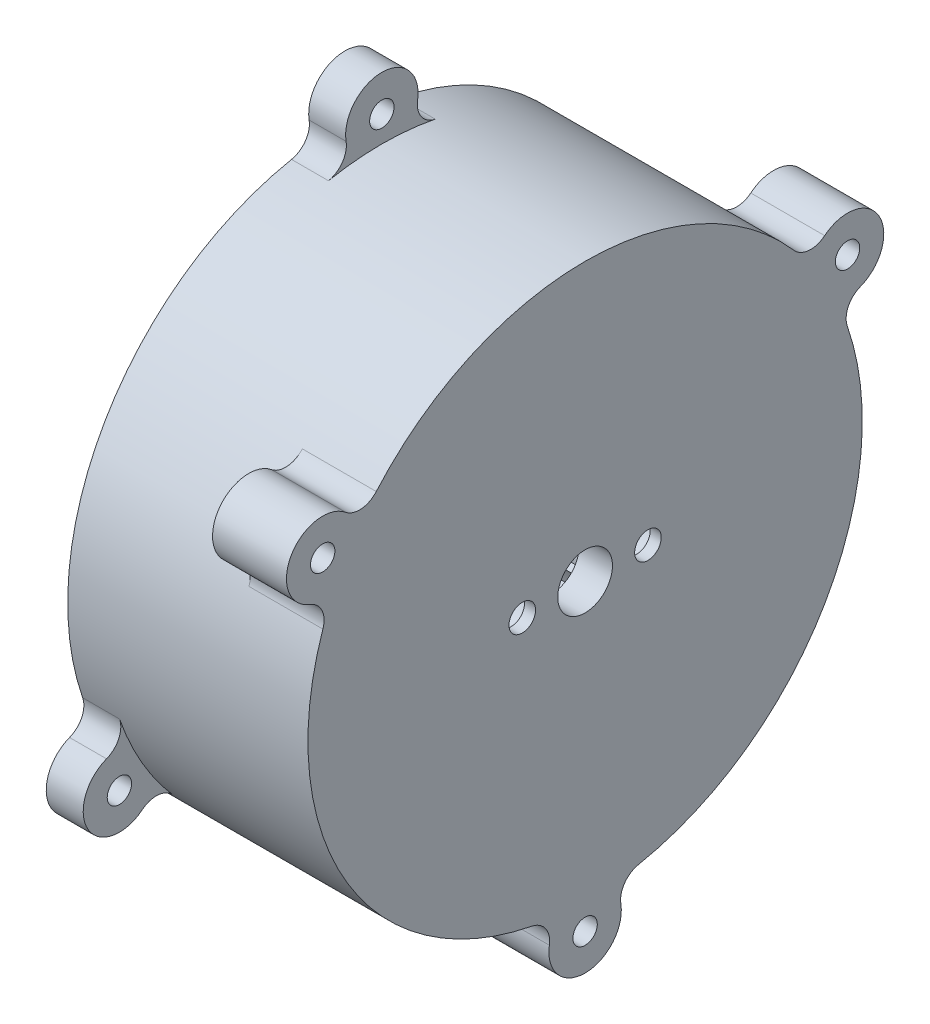
SolidWorks part; units mm, degrees
ref_plane "Plane1" through (0, 0, 0) normal (0, 0, 1) x (1, 0, 0)
ref_plane "Plane2" through (0, 0, 0) normal (0, 1, 0) x (1, 0, 0)
ref_plane "Plane3" through (0, 0, 0) normal (1, 0, 0) x (0, 0, -1)
sketch "HoldingSke" plane through (0, 0, 0) normal (0, 1, 0) x (1, 0, 0)
  line L0 (0, 0) -> (0.4589, -0.6553)
  line L1 (-15, 0) -> (100, 0) construction
  line L2 (0, 0) -> (-2.1039, 2.3779)
  line L3 (0, 0) -> (-11.863, 4.5341)
  line L4 (0, 0) -> (4.9534, 7.0742)
  line L5 (0, 0) -> (-23.7986, -8.8762)
  line L6 (0, 0) -> (-10.5278, -7.1032)
  line L7 (-2.1039, 2.3779) -> (3.3635, 27.1825)
  line L8 (-76.2, 3.6279) -> (-54.61, 3.6279)
  line L9 (-67.7845, 28.3722) -> (-49.3413, 33.142)
  line L10 (-76.2, 71.12) -> (104.1128, 71.12)
  line L11 (0, 0) -> (-28, 0)
  line L12 (-76.2, 101.6) -> (-76.155, 101.6)
  line L13 (24.9733, 27.94) -> (52.9518, 28.4284)
  line L14 (24.9733, 27.94) -> (24.9743, 27.94)
  line L15 (24.9733, 27.94) -> (100.4006, 29.5858)
  circle A0 centre (0, 0) radius 37.5
  circle A1 centre (0, 0) radius 12.7
  circle A2 centre (0, 0) radius 12.7
  dimension "Num_teeth" = 55
  dimension "Pitch_radius" = 180.3128
  dimension "Width" = 28
  dimension "Diameter" = 75
sketch "BasProSke" plane through (0, 0, 0) normal (0, 1, 0) x (1, 0, 0)
  line L0 (-10, 0) -> (60, 0) construction
  line L1 (0, 33.125) -> (0, 37.5)
  line L2 (0, 33.125) -> (28, 33.125)
  line L3 (28, 33.125) -> (28, 37.5)
  line L4 (28, 37.5) -> (0, 37.5)
  dimension "Thickness" = 28
  dimension "Diameter" = 75
revolve "Base-Revolve" add sketch "BasProSke" angle 360 about L0
sketch "TooCutSke" plane through (0, 0, 0) normal (1, 0, 0) x (0, 0, -1)
  line L3 (1.0941, 34.3576) -> (1.0941, 53.6633) construction
  line L4 (0, 0) -> (0, 59.563) construction
  line L5 (0, 0) -> (-3.9007, 68.2161) construction
  line L6 (-15.2783, 29.1274) -> (36.0712, 32.0636) construction
  circle A0 centre (0, 0) radius 34.375 construction
  circle A1 centre (0, 0) radius 35.9385 construction
  circle A2 centre (0, 0) radius 29.9521 construction
  circle A3 centre (0, 0) radius 33.0996 construction
  arc A4 (1.4514, 33.0678) -> (0.5036, 35.935) centre (-15.2783, 29.1274) ccw
  arc A5 (1.4514, 33.0678) -> (-1.4514, 33.0678) centre (0, 0) ccw
  arc A6 (0.5036, 35.935) -> (-0.5036, 35.935) centre (0, 0) ccw
  arc A7 (-0.5036, 35.935) -> (-1.4514, 33.0678) centre (15.2783, 29.1274) ccw
extrude "ToothCut" cut sketch "TooCutSke" along normal through all
fillet "Breaks" [suppressed] radius 0.125
fillet "RootFillets" [suppressed] radius 0.3135
pattern_circular "TeethCuts" count 55 every 6.545 about axis through (-10, 0, 0) along (1, 0, 0) of "RootFillets", "Breaks", "ToothCut"
sketch "Sketch1" plane through (28, 0, 0) normal (1, 0, 0) x (0, 0, -1)
  circle A0 centre (0, 0) radius 37.5
extrude "Boss-Extrude1" add sketch "Sketch1" along normal blind 4.5
sketch "Sketch2" plane through (32.5, 0, 0) normal (1, 0, 0) x (0, 0, -1)
  circle A0 centre (0, 0) radius 3.7
  circle A1 centre (-8.5, 0) radius 1.8
  circle A2 centre (8.5, 0) radius 1.8
  dimension "D1" = 7.4
  dimension "D2" = 3.6
  dimension "D3" = 8.5
  dimension "D4" = 8.5
extrude "Cut-Extrude1" cut sketch "Sketch2" against normal blind 4.5
sketch "Sketch3" plane through (28, 0, 0) normal (-1, 0, 0) x (0, 0, 1)
  circle A0 centre (-8.5, 0) radius 3.25
  circle A1 centre (8.5, 0) radius 3.25
  dimension "D1" = 6.5
extrude "Cut-Extrude2" cut sketch "Sketch3" against normal blind 3
sketch "Sketch4" plane through (0, 0, 0) normal (-1, 0, 0) x (0, 0, 1)
  line L0 (0, 0) -> (0, 45.9) construction
  circle A0 centre (0, 41) radius 1.65
  circle A1 centre (0, 0) radius 3.7 construction
  circle A2 centre (35.507, -20.5) radius 1.65
  circle A3 centre (-35.507, -20.5) radius 1.65
  arc A4 (-3.2765, 37.3566) -> (3.2765, 37.3566) centre (0, 41) cw
  circle A5 centre (0, 0) radius 37.5 construction
  arc A6 (-3.2765, 37.3566) -> (3.2765, 37.3566) centre (0, 0) cw
  arc A7 (33.99, -15.8408) -> (30.7135, -21.5158) centre (35.507, -20.5) cw
  arc A8 (33.99, -15.8408) -> (30.7135, -21.5158) centre (0, 0) cw
  arc A9 (-30.7135, -21.5158) -> (-33.99, -15.8408) centre (-35.507, -20.5) cw
  arc A10 (-30.7135, -21.5158) -> (-33.99, -15.8408) centre (0, 0) cw
  point P11 (0, 0)
  point P28 (0, 0)
  dimension "D1" = 3.3
  dimension "D2" = 41
  dimension "D5" = 3
  dimension "D4" = 45.9
  dimension "D3" = 3
extrude "Boss-Extrude2" add sketch "Sketch4" against normal blind 5
fillet "Fillet1" radius 3 6 edges at (2.5, -21.5158, -30.7135) (2.5, -21.5158, 30.7135) (2.5, -15.8408, 33.99) (2.5, 37.3566, 3.2765) (2.5, -15.8408, -33.99) (2.5, 37.3566, -3.2765)
sketch "Sketch5" plane through (32.5, 0, 0) normal (1, 0, 0) x (0, 0, -1)
  line L0 (0, 0) -> (35.507, 20.5) construction
  line L1 (0, 0) -> (0, 41) construction
  circle A1 centre (35.507, 20.5) radius 1.65
  circle A2 centre (0, -41) radius 1.65
  circle A3 centre (-35.507, 20.5) radius 1.65
  arc A4 (33.99, 15.8408) -> (30.7135, 21.5158) centre (35.507, 20.5) ccw
  circle A5 centre (0, 0) radius 37.5 construction
  arc A6 (30.7135, 21.5158) -> (33.99, 15.8408) centre (0, 0) cw
  arc A7 (-3.2765, -37.3566) -> (3.2765, -37.3566) centre (0, -41) ccw
  arc A8 (3.2765, -37.3566) -> (-3.2765, -37.3566) centre (0, 0) cw
  arc A9 (-30.7135, 21.5158) -> (-33.99, 15.8408) centre (-35.507, 20.5) ccw
  arc A10 (-33.99, 15.8408) -> (-30.7135, 21.5158) centre (0, 0) cw
  point P13 (0, 0)
  point P26 (0, 0)
  dimension "D2" = 3.3
  dimension "D4" = 3
  dimension "D1" = 60
  dimension "D3" = 3
extrude "Boss-Extrude3" add sketch "Sketch5" against normal blind 10
fillet "Fillet2" radius 3 6 edges at (27.5, 15.8408, 33.99) (27.5, -37.3566, 3.2765) (27.5, -37.3566, -3.2765) (27.5, 21.5158, 30.7135) (27.5, 15.8408, -33.99) (27.5, 21.5158, -30.7135)
equation "' \"Module@HoldingSke\" = 6.35"
equation "' \"Num_teeth@HoldingSke\" = 24"
equation "' \"Ap@HoldingSke\" =  14.5"
equation "' \"Ap@HoldingSke\" = 14.5"
equation "' \"Width@HoldingSke\" = 12"
equation "' \"Diameter@HoldingSke\" = 8 * 25.4"
equation "' \"Show_teeth@HoldingSke\" = 100"
equation "' \"Backlash@HoldingSke\" = 0.009 * 25.4"
equation "' \"Addendum_fac@HoldingSke\" = 1.0"
equation "' \"Dedendum_fac@HoldingSke\" = 1.25"
equation "' \"Dedendum_add@HoldingSke\" = 0.00005 * 25.4"
equation "' \"Clearance_fac@HoldingSke\" = 0.25"
equation "\"Pitch@HoldingSke\" = 1 / \"Module@HoldingSke\" "
equation "\"Overcut_dia@TooCutSke\" = (\"Num_teeth@HoldingSke\" - 2 * \"Addendum_fac@HoldingSke\") / \"Pitch@HoldingSke\" - 0.002 * 25.4"
equation "\"Pitch_dia@TooCutSke\" = \"Num_teeth@HoldingSke\" / \"Pitch@HoldingSke\""
equation "\"Base_dia@TooCutSke\" = \"Num_teeth@HoldingSke\" / \"Pitch@HoldingSke\" * cos((\"Ap@HoldingSke\"  * 3.14159265 / 180)) * 0.90"
equation "\"Root_dia@TooCutSke\" = \"Num_teeth@HoldingSke\"  / \"Pitch@HoldingSke\" + 2 *  \"Dedendum_fac@HoldingSke\"/ \"Pitch@HoldingSke\" + \"Dedendum_add@HoldingSke\" * 2"
equation "\"Half_ang@TooCutSke\" = 180 / \"Num_teeth@HoldingSke\""
equation "\"Half_CT@TooCutSke\" = \"Num_teeth@HoldingSke\" / \"Pitch@HoldingSke\" * sin((3.14159265 / 2 / \"Num_teeth@HoldingSke\")) / 2 + 10 * \"Backlash@HoldingSke\" / 4"
equation "\"Flank_rad@TooCutSke\" = \"Num_teeth@HoldingSke\" / \"Pitch@HoldingSke\" / 4"
equation "\"Radius@RootFillets\"= \"Clearance_fac@HoldingSke\" / \"Pitch@HoldingSke\" + \"Dedendum_add@HoldingSke\""
equation "\"Break_rad@Breaks\" = 0.02 / \"Pitch@HoldingSke\" * 5"
equation "\"Num_teeth@TeethCuts\" = int( \"Show_teeth@HoldingSke\" ) + 1"
equation "\"Num_teeth@TeethCuts\" = ((sgn( \"Num_teeth@TeethCuts\" - \"Num_teeth@HoldingSke\" )-1)*( \"Num_teeth@TeethCuts\" - \"Num_teeth@HoldingSke\" ))/-2+ \"Num_teeth@HoldingSke\""
equation "\"Num_teeth@TeethCuts\" = ((sgn( \"Num_teeth@TeethCuts\" - 2.0)+1)*( \"Num_teeth@TeethCuts\" - 2.0))/2 +2.0"
equation "\"Angle@TeethCuts\" = 360.0 / \"Num_teeth@HoldingSke\""
equation "\"Diameter@BasProSke\" = \"Num_teeth@HoldingSke\"  / \"Pitch@HoldingSke\" + 2 *  \"Dedendum_fac@HoldingSke\"/ \"Pitch@HoldingSke\" + \"Dedendum_add@HoldingSke\" * 2 + 0.002 * 25.4"
equation "\"Diameter@BasProSke\" = ((sgn( \"Diameter@BasProSke\"  - \"Diameter@HoldingSke\" )+1)*( \"Diameter@BasProSke\"  - \"Diameter@HoldingSke\" ))/2 + \"Diameter@HoldingSke\""
equation "\"Inside_diameter@BasProSke\" =  (\"Num_teeth@HoldingSke\" - 2 * \"Addendum_fac@HoldingSke\") / \"Pitch@HoldingSke\" "
equation "\"Thickness@BasProSke\"  = \"Width@HoldingSke\""
